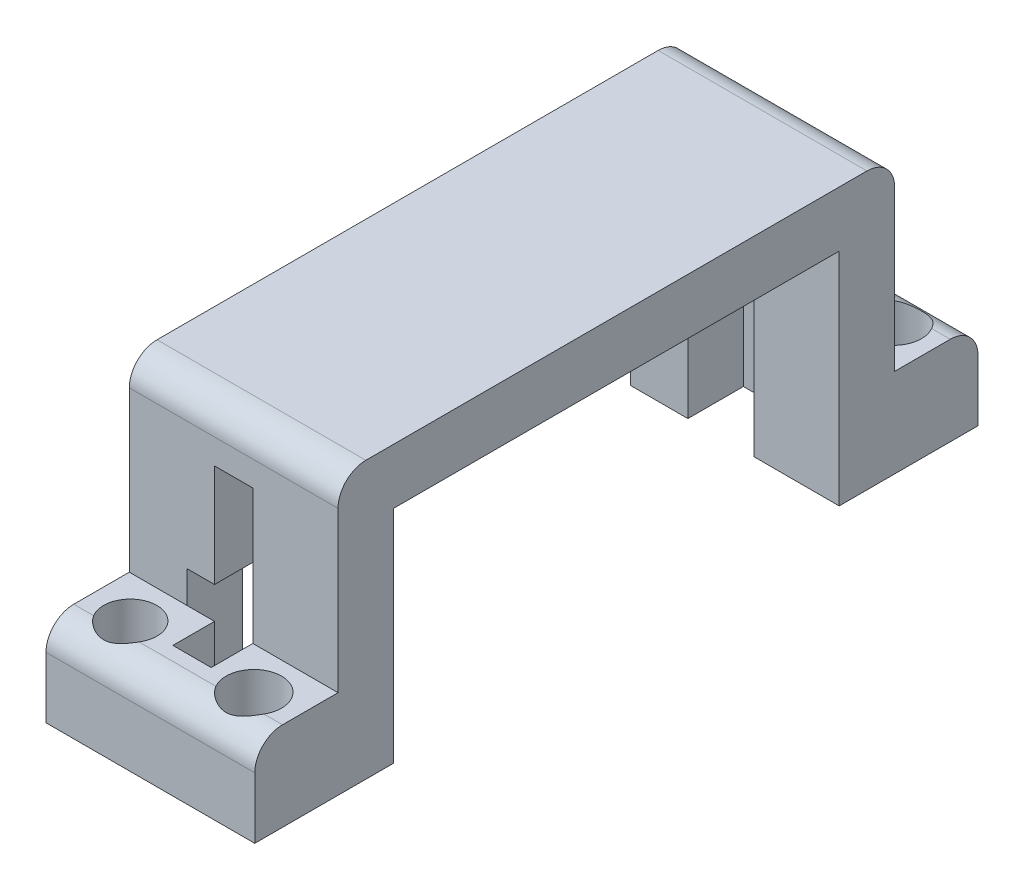
SolidWorks part; units mm, degrees
ref_plane "Front Plane" through (0, 0, 0) normal (0, 0, 1) x (1, 0, 0)
ref_plane "Top Plane" through (0, 0, 0) normal (0, 1, 0) x (1, 0, 0)
ref_plane "Right Plane" through (0, 0, 0) normal (1, 0, 0) x (0, 0, -1)
sketch "Sketch1" plane through (0, 0, 0) normal (1, 0, 0) x (0, 0, -1)
  line L0 (-25.0625, 0) -> (25.0625, 0)
  line L1 (-25.0625, 0) -> (-25.0625, -20.875)
  line L2 (-25.0625, -24.875) -> (-20.0625, -24.875)
  line L3 (-20.0625, -24.875) -> (-20.0625, -5)
  line L4 (-20.0625, -5) -> (20.0625, -5)
  line L5 (20.0625, -5) -> (20.0625, -24.875)
  line L6 (20.0625, -24.875) -> (25.0625, -24.875)
  line L7 (25.0625, -20.875) -> (25.0625, 0)
  line L8 (-20.0625, 0) -> (-20.0625, -5) construction
  line L10 (-25.0625, -24.875) -> (-32.5625, -24.875)
  line L12 (-25.0625, -20.875) -> (-32.5625, -20.875)
  line L13 (-32.5625, -24.875) -> (-32.5625, -20.875)
  line L14 (25.0625, -24.875) -> (32.5625, -24.875)
  line L16 (25.0625, -20.875) -> (32.5625, -20.875)
  line L17 (32.5625, -24.875) -> (32.5625, -20.875)
  point P4 (0, 0)
  dimension "D1" = 40.125
  dimension "D2" = 19.875
  dimension "D3" = 5
  dimension "D4" = 4
  dimension "D5" = 7.5
extrude "Boss-Extrude1" add sketch "Sketch1" along normal blind 18.8
sketch "Sketch2" plane through (0, 0, 32.5625) normal (0, 0, 1) x (1, 0, 0)
  line L0 (0, -24.875) -> (7.675, -24.875) construction
  line L1 (18.8, -24.875) -> (0, -24.875) construction
  line L2 (7.675, -24.875) -> (7.675, -4.75)
  line L3 (7.675, -4.75) -> (11.125, -4.75)
  line L4 (11.125, -4.75) -> (11.125, -24.875)
  line L5 (11.125, -24.875) -> (7.675, -24.875)
  dimension "D1" = 7.675
  dimension "D2" = 3.45
  dimension "D3" = 20.125
extrude "Cut-Extrude1" cut sketch "Sketch2" against normal through all
sketch "Sketch3" plane through (0, -20.875, 0) normal (0, 1, 0) x (1, 0, 0)
  line L0 (2.121, -27.1351) -> (5.554, -30.4899) construction
  line L1 (5.554, -27.1351) -> (2.121, -30.4899) construction
  line L2 (13.246, -27.1351) -> (16.679, -30.4899) construction
  line L3 (16.679, -27.1351) -> (13.246, -30.4899) construction
  line L4 (2.121, 30.4899) -> (5.554, 27.1351) construction
  line L5 (2.121, 27.1351) -> (5.554, 30.4899) construction
  line L6 (13.246, 30.4899) -> (16.679, 27.1351) construction
  line L7 (16.679, 30.4899) -> (13.246, 27.1351) construction
  circle A0 centre (3.8375, -28.8125) radius 2.4
  circle A2 centre (14.9625, -28.8125) radius 2.4
  circle A3 centre (14.9625, 28.8125) radius 2.4
  circle A4 centre (3.8375, 28.8125) radius 2.4
  dimension "D1" = 2
  dimension "D3" = 4.8
  dimension "D2" = 2
extrude "Cut-Extrude2" cut sketch "Sketch3" against normal up to next contours A0 | A2 | A3 | A4
sketch "Sketch4" plane through (7.675, 0, 0) normal (1, 0, 0) x (0, 0, -1)
  line L0 (-20.0625, -24.875) -> (-20.0625, -15.75)
  line L1 (-20.0625, -24.875) -> (-20.0625, -5) construction
  line L2 (-20.0625, -15.75) -> (-20.0625, -14)
  line L3 (-20.0625, -14) -> (-25.0625, -14)
  line L4 (-25.0625, 0) -> (-25.0625, -20.875) construction
  line L5 (-25.0625, -14) -> (-25.0625, -15.75)
  line L7 (-25.0625, -15.75) -> (-25.0625, -24.875)
  line L8 (-32.5625, -24.875) -> (-20.0625, -24.875) construction
  line L9 (-25.0625, -24.875) -> (-20.0625, -24.875)
  dimension "D1" = 9.125
  dimension "D2" = 1.75
sketch "Sketch7" plane through (7.675, 0, 0) normal (1, 0, 0) x (0, 0, -1)
  line L0 (-32.5625, -24.875) -> (-20.0625, -24.875) construction
  line L2 (-32.5625, -20.875) -> (-28.8125, -20.875)
  line L3 (-32.5625, -20.875) -> (-32.5625, -24.875)
  line L4 (-32.5625, -24.875) -> (-28.8125, -24.875)
  line L5 (-28.8125, -20.875) -> (-28.8125, -24.875)
  line L6 (-26.4125, -20.875) -> (-31.2125, -20.875) construction
extrude "Boss-Extrude2" add sketch "Sketch7" along normal up to next
mirror "Mirror1" about plane through (0, 0, 0) normal (0, 0, 1) of "Boss-Extrude2"
extrude "Cut-Extrude8" cut sketch "Sketch4" against normal blind 2.5
mirror "Mirror2" about plane through (0, 0, 0) normal (0, 0, 1) of "Cut-Extrude8", "Mirror1"
sketch "Sketch8" plane through (0, -20.875, 0) normal (0, 1, 0) x (1, 0, 0)
  line L0 (17.3625, 28.8125) -> (12.5625, 28.8125) construction
  line L1 (17.3625, -28.8125) -> (12.5625, -28.8125) construction
  circle A0 centre (14.9625, 28.8125) radius 2.5
  circle A1 centre (14.9625, -28.8125) radius 2.5
  dimension "D1" = 5
extrude "Cut-Extrude9" cut sketch "Sketch8" against normal through all
sketch "Sketch9" plane through (0, -20.875, 0) normal (0, 1, 0) x (1, 0, 0)
  line L9 (11.125, -28.8125) -> (7.675, -28.8125)
  line L10 (7.675, -28.8125) -> (7.675, -25.0625)
  line L11 (7.675, -25.0625) -> (5.175, -25.0625)
  line L12 (5.175, -25.0625) -> (0, -25.0625)
  line L13 (0, -25.0625) -> (0, -32.5625)
  line L14 (0, -32.5625) -> (18.8, -32.5625)
  line L15 (18.8, -32.5625) -> (18.8, -25.0625)
  line L16 (18.8, -25.0625) -> (11.125, -25.0625)
  line L17 (11.125, -25.0625) -> (11.125, -28.8125)
  line L18 (11.125, -28.8125) -> (7.675, -28.8125)
  line L19 (7.675, -28.8125) -> (7.675, -25.0625)
  line L20 (7.675, -25.0625) -> (5.175, -25.0625)
  line L21 (5.175, -25.0625) -> (0, -25.0625)
  line L22 (0, -25.0625) -> (0, -32.5625)
  line L23 (0, -32.5625) -> (18.8, -32.5625)
  line L24 (18.8, -32.5625) -> (18.8, -25.0625)
  line L25 (18.8, -25.0625) -> (11.125, -25.0625)
  line L26 (11.125, -25.0625) -> (11.125, -28.8125)
  line L27 (11.125, 25.0625) -> (18.8, 25.0625)
  line L28 (18.8, 25.0625) -> (18.8, 32.5625)
  line L29 (18.8, 32.5625) -> (0, 32.5625)
  line L30 (0, 32.5625) -> (0, 25.0625)
  line L31 (0, 25.0625) -> (5.175, 25.0625)
  line L32 (5.175, 25.0625) -> (7.675, 25.0625)
  line L33 (7.675, 25.0625) -> (7.675, 28.8125)
  line L34 (7.675, 28.8125) -> (11.125, 28.8125)
  line L35 (11.125, 28.8125) -> (11.125, 25.0625)
  line L36 (11.125, 25.0625) -> (18.8, 25.0625)
  line L37 (18.8, 25.0625) -> (18.8, 32.5625)
  line L38 (18.8, 32.5625) -> (0, 32.5625)
  line L39 (0, 32.5625) -> (0, 25.0625)
  line L40 (0, 25.0625) -> (5.175, 25.0625)
  line L41 (5.175, 25.0625) -> (7.675, 25.0625)
  line L42 (7.675, 25.0625) -> (7.675, 28.8125)
  line L43 (7.675, 28.8125) -> (11.125, 28.8125)
  line L44 (11.125, 28.8125) -> (11.125, 25.0625)
  circle A0 centre (3.8375, 28.8125) radius 2.4 construction
  circle A1 centre (3.8375, 28.8125) radius 2.4
  circle A2 centre (14.9625, 28.8125) radius 2.5 construction
  circle A3 centre (14.9625, 28.8125) radius 2.5
  circle A4 centre (3.8375, -28.8125) radius 2.4 construction
  circle A5 centre (3.8375, -28.8125) radius 2.4
  circle A6 centre (14.9625, -28.8125) radius 2.5 construction
  circle A7 centre (14.9625, -28.8125) radius 2.5
  dimension "D1" = 0
  dimension "D2" = 0
extrude "Boss-Extrude3" add sketch "Sketch9" along normal blind 4
mirror "Mirror6" about plane through (0, 0, 0) normal (0, 0, 1) of "Boss-Extrude3"
fillet "Fillet1" radius 2.5 4 edges at (9.4, -16.875, 32.5625) (9.4, 0, 25.0625) (9.4, 0, -25.0625) (9.4, -16.875, -32.5625)
